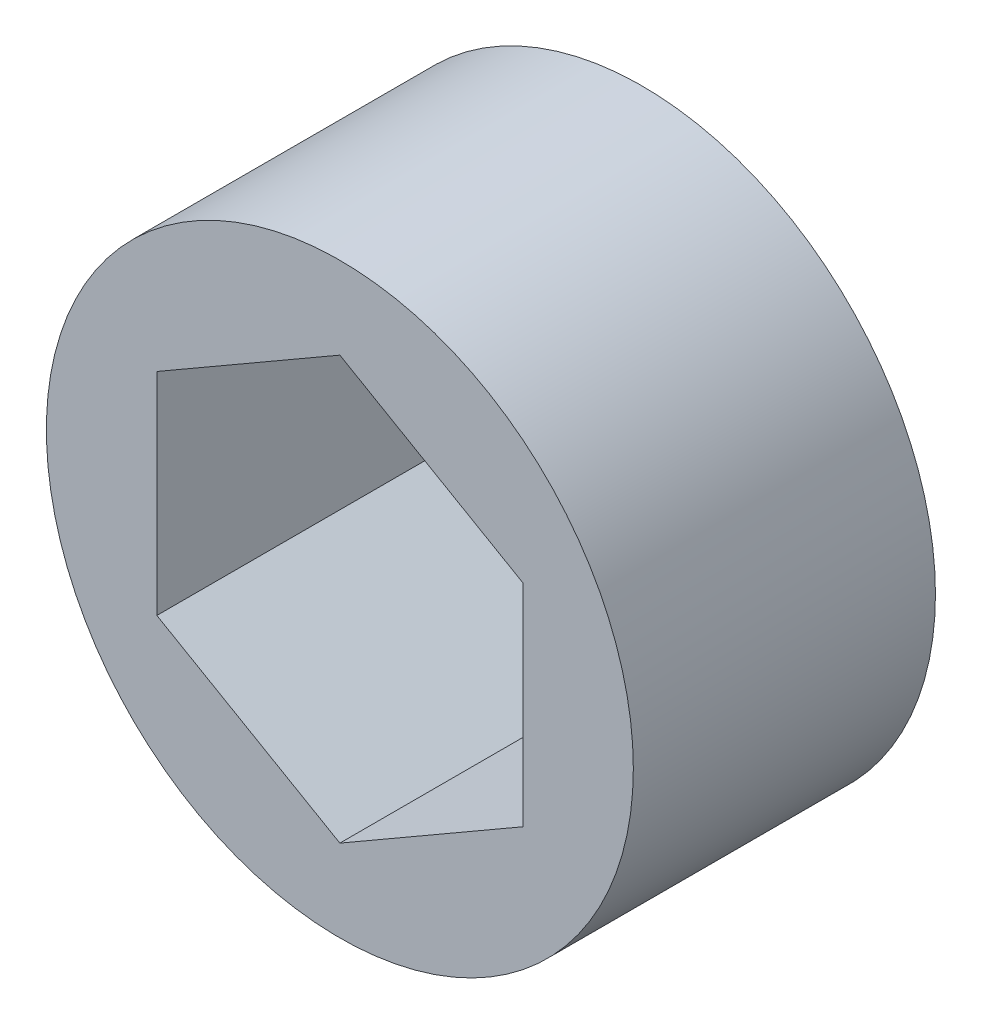
SolidWorks part; units mm, degrees
material "Nylon 101"
ref_plane "Front Plane" through (0, 0, 0) normal (0, 0, 1) x (1, 0, 0)
ref_plane "Top Plane" through (0, 0, 0) normal (0, 1, 0) x (1, 0, 0)
ref_plane "Right Plane" through (0, 0, 0) normal (1, 0, 0) x (0, 0, -1)
sketch "Sketch1" plane through (0, 0, 0) normal (0, 0, 1) x (1, 0, 0)
  line L1 (6.731, 3.8861) -> (0, 7.7723)
  line L2 (0, 7.7723) -> (-6.731, 3.8861)
  line L3 (-6.731, 3.8861) -> (-6.731, -3.8861)
  line L4 (-6.731, -3.8861) -> (0, -7.7723)
  line L5 (0, -7.7723) -> (6.731, -3.8861)
  line L6 (6.731, -3.8861) -> (6.731, 3.8861)
  circle A0 centre (0, 0) radius 6.731 construction
  circle A1 centre (0, 0) radius 10.795
  dimension "D1" = 13.462
  dimension "D2" = 21.59
extrude "Boss-Extrude1" add sketch "Sketch1" along normal blind 11.1125
